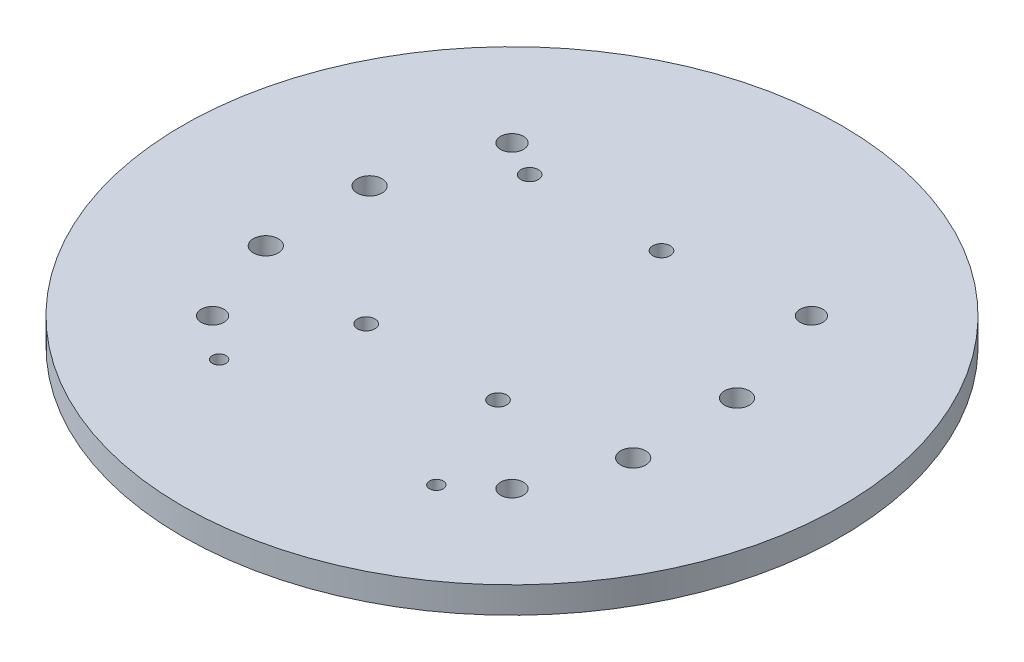
SolidWorks part; units mm, degrees
other "Markup1"
sketch "Sketch21" plane through (-65.5, -15.05, -60) normal (-0.0927, -0.2854, -0.9539) x (0.9951, -0.0609, -0.0785)
material "6061 Alloy"
ref_plane "Front Plane" through (0, 0, 0) normal (0, 0, 1) x (1, 0, 0)
ref_plane "Top Plane" through (0, 0, 0) normal (0, 1, 0) x (1, 0, 0)
ref_plane "Right Plane" through (0, 0, 0) normal (1, 0, 0) x (0, 0, -1)
sketch "Sketch1" plane through (0, 0, 0) normal (0, 1, 0) x (1, 0, 0)
  circle A0 centre (0, 0) radius 79.375
  dimension "D1" = 158.75
extrude "Boss-Extrude1" add sketch "Sketch1" along normal mid plane 6.35
sketch "Sketch2" plane through (0, -3.175, 0) normal (0, -1, 0) x (1, 0, 0)
  circle A0 centre (0, 0) radius 12.065
  circle A1 centre (0, 0) radius 79.375 construction
  dimension "D1" = 24.13
sketch "Sketch5" plane through (0, 3.175, 0) normal (0, 1, 0) x (1, 0, 0)
  circle A0 centre (0, 0) radius 10.4
  circle A1 centre (0, 0) radius 79.375 construction
  dimension "D1" = 20.8
hole_wizard "Tap Drill for M5x0.8 Tap1" positions "Sketch22" profile "Sketch23" hole size "M5x0.8" standard "ANSI Metric" end condition through all
sketch "Sketch22" plane through (0, 3.175, 0) normal (0, 1, 0) x (1, 0, 0)
  point P0 (-27.3188, 31.5712)
  point P3 (4.4312, 31.5712)
  point P6 (-15.875, -19.2459)
  point P9 (15.875, -19.2459)
  dimension "D1" = 31.75
  dimension "D2" = 31.5712
  dimension "D3" = 4.4312
  dimension "D4" = 31.75
  dimension "D5" = 19.2459
  dimension "D6" = 15.875
sketch "Sketch23" plane through (-27.3188, 3.175, -31.5712) normal (1, 0, 0) x (0, 0, 1)
  line L0 (0, 0) -> (0, 6.35)
  line L1 (0, 6.35) -> (2.1, 6.35)
  line L2 (2.1, 6.35) -> (2.1, 0)
  line L5 (2.1, 0) -> (0, 0)
  line L11 (0, -6.35) -> (0, 107.95) construction
  dimension "Thru Hole Dia." = 4.2
  dimension "Thru Hole Depth" = 6.35
hole_wizard "Tap Drill for M7x1.0 Tap1" positions "Sketch24" profile "Sketch25" hole size "M7x1.0" standard "ANSI Metric" end condition through all
sketch "Sketch24" plane through (0, 3.175, 0) normal (0, 1, 0) x (1, 0, 0)
  point P0 (-44.245, 9.9416)
  point P3 (-44.245, -15.0584)
  point P6 (44.245, 9.9416)
  point P9 (44.245, -15.0584)
  dimension "D1" = 25
  dimension "D2" = 44.245
  dimension "D3" = 9.9416
  dimension "D4" = 25
  dimension "D5" = 44.245
  dimension "D6" = 15.0584
sketch "Sketch25" plane through (-44.245, 3.175, -9.9416) normal (1, 0, 0) x (0, 0, 1)
  line L0 (0, 0) -> (0, 6.35)
  line L1 (0, 6.35) -> (3, 6.35)
  line L2 (3, 6.35) -> (3, 0)
  line L5 (3, 0) -> (0, 0)
  line L11 (0, -6.35) -> (0, 107.95) construction
  dimension "Thru Hole Dia." = 6
  dimension "Thru Hole Depth" = 6.35
hole_wizard "Tap Drill for M4x0.7 Tap1" positions "Sketch26" profile "Sketch27" hole size "M4x0.7" standard "ANSI Metric" end condition through all
sketch "Sketch26" plane through (0, 3.175, 0) normal (0, 1, 0) x (1, 0, 0)
  point P0 (-26.155, -44.3844)
  point P3 (26.155, -44.3844)
  dimension "D1" = 52.31
  dimension "D2" = 44.3844
  dimension "D3" = 26.155
sketch "Sketch27" plane through (-26.155, 3.175, 44.3844) normal (1, 0, 0) x (0, 0, 1)
  line L0 (0, 0) -> (0, 6.35)
  line L1 (0, 6.35) -> (1.65, 6.35)
  line L2 (1.65, 6.35) -> (1.65, 0)
  line L5 (1.65, 0) -> (0, 0)
  line L11 (0, -6.35) -> (0, 107.95) construction
  dimension "Thru Hole Dia." = 3.3
  dimension "Thru Hole Depth" = 6.35
sketch "Sketch28" plane through (0, 3.175, 0) normal (0, 1, 0) x (1, 0, 0)
  circle A0 centre (0, 0) radius 51
  circle A1 centre (35.8572, -36.2665) radius 4.2952
  dimension "D1" = 102
hole_wizard "M5 Clearance Hole1" positions "Sketch29" profile "Sketch30" hole size "M5" standard "ANSI Metric" end condition through all
sketch "Sketch29" plane through (0, 3.175, 0) normal (0, 1, 0) x (1, 0, 0)
  line L0 (-36.0624, 36.0624) -> (-36.0624, -36.0624) construction
  line L2 (-36.0624, 36.0624) -> (36.0624, 36.0624) construction
  line L3 (36.0624, 36.0624) -> (36.0624, -36.0624) construction
  line L4 (36.0624, -36.0624) -> (-36.0624, -36.0624) construction
  circle A0 centre (0, 0) radius 51 construction
  point P0 (-36.0624, 36.0624)
  point P4 (-36.0624, -36.0624)
  point P6 (36.0624, -36.0624)
  point P8 (36.0624, 36.0624)
sketch "Sketch30" plane through (-36.0624, 3.175, -36.0624) normal (1, 0, 0) x (0, 0, 1)
  line L0 (0, 0) -> (0, 6.35)
  line L1 (0, 6.35) -> (2.75, 6.35)
  line L2 (2.75, 6.35) -> (2.75, 0)
  line L5 (2.75, 0) -> (0, 0)
  line L11 (0, -6.35) -> (0, 107.95) construction
  dimension "Thru Hole Dia." = 5.5
  dimension "Thru Hole Depth" = 6.35
